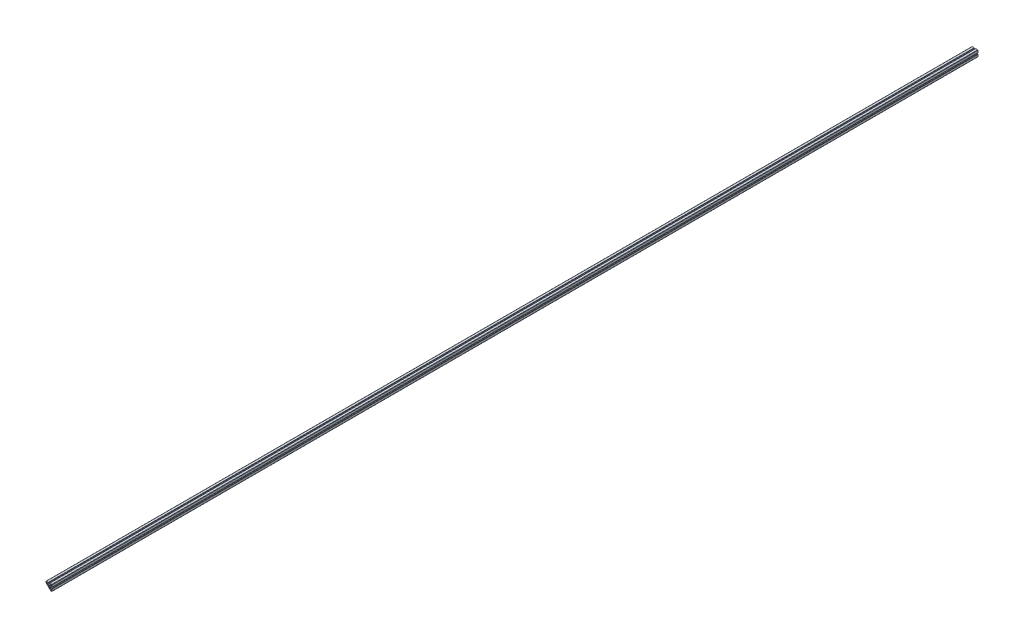
SolidWorks part; units mm, degrees
ref_plane "Front Plane" through (0, 0, 0) normal (0, 0, 1) x (1, 0, 0)
ref_plane "Top Plane" through (0, 0, 0) normal (0, 1, 0) x (1, 0, 0)
ref_plane "Right Plane" through (0, 0, 0) normal (1, 0, 0) x (0, 0, -1)
sketch "Sketch1" plane through (0, 0, 0) normal (0, 0, 1) x (1, 0, 0)
  line L0 (0, 0) -> (20, 20) construction
  line L1 (0, 0) -> (0, 20) construction
  line L2 (0, -20) -> (0, 20) construction
  line L3 (20, 0) -> (-20, 0) construction
  line L4 (4.05, 20) -> (-4.05, 20) construction
  line L5 (-20, 20) -> (-4.05, 20) construction
  line L6 (0, 0) -> (-20, 20) construction
  line L7 (5.4787, 7.6) -> (-5.4787, 7.6) construction
  line L8 (5.4787, 7.6) -> (11.2, 13.3213) construction
  line L9 (11.2, 13.3213) -> (11.2, 18.5) construction
  line L10 (11.2, 18.5) -> (7.05, 18.5) construction
  line L11 (7.05, 18.5) -> (7.05, 17.5) construction
  line L12 (4.05, 20) -> (4.05, 17.5) construction
  line L13 (4.05, 17.5) -> (7.05, 17.5) construction
  line L14 (-5.4787, 7.6) -> (-11.2, 13.3213) construction
  line L15 (-11.2, 13.3213) -> (-11.2, 18.5) construction
  line L16 (-11.2, 18.5) -> (-7.05, 18.5) construction
  line L17 (-7.05, 18.5) -> (-7.05, 17.5) construction
  line L18 (-4.05, 17.5) -> (-7.05, 17.5) construction
  line L19 (-4.05, 20) -> (-4.05, 17.5) construction
  line L21 (-20, 20) -> (-20, 10.5787) construction
  line L22 (-20, 10.5787) -> (-4.7107, -4.7107) construction
  line L23 (0, 0) -> (-4.7107, -4.7107) construction
  line L24 (-7.6, 5.4787) -> (-13.3213, 11.2) construction
  line L25 (-13.3213, 11.2) -> (-18.5, 11.2) construction
  line L26 (-18.5, 11.2) -> (-7.6, 0.3) construction
  line L27 (-7.6, 0.3) -> (-7.6, 5.4787) construction
  line L28 (-13.05, 5.75) -> (-14.1107, 4.6893) construction
  line L29 (11.2, 20) -> (11.2, 18.5) construction
  line L30 (4.05, 20) -> (20, 20) construction
  line L31 (-18.5, 18.5) -> (-14.5, 18.5) construction
  line L32 (-18.5, 18.5) -> (-18.5, 14.5) construction
  line L33 (-18.5, 14.5) -> (-14.5, 14.5) construction
  line L34 (-14.5, 18.5) -> (-14.5, 14.5) construction
  line L35 (-18.5, 18.5) -> (-14.5, 14.5) construction
  line L36 (-18.5, 14.5) -> (-14.5, 18.5) construction
  line L37 (18.5, 14.5) -> (14.5, 14.5) construction
  line L38 (18.5, 18.5) -> (18.5, 14.5) construction
  line L39 (18.5, 18.5) -> (14.5, 18.5) construction
  line L40 (14.5, 18.5) -> (14.5, 14.5) construction
  circle A0 centre (0, 0) radius 4.45 construction
  point P4 (0, 0)
  point P7 (0, 0)
  point P10 (0, 0)
  point P13 (0, 0)
  point P18 (0, 20)
  point P22 (0, 20)
  point P25 (0, 7.6)
  point P49 (-16.5, 16.5)
  dimension "D2" = 8.9
  dimension "D3" = 45
  dimension "D4" = 8.1
  dimension "D8" = 3
  dimension "D9" = 1
  dimension "D11" = 1.5
  dimension "D12" = 1.5
  dimension "D13" = 4
  dimension "D5" = 22.4
  dimension "D7" = 1.5
  dimension "D10" = 40
  dimension "D14" = 12.4
  dimension "D6" = 40
sketch "Sketch2" plane through (0, 0, 0) normal (1, 0, 0) x (0, 0, -1)
  line L0 (3048, 0) -> (-3048, 0) construction
  line L1 (-3008, -20) -> (-3008, 20) construction
  line L2 (3008, -20) -> (3008, 20) construction
  point P3 (0, 0)
  point P7 (-3008, 0)
  point P10 (3008, 0)
  dimension "Length" = 6096
  dimension "D1" = 40
  dimension "D2" = 40
  dimension "D3" = 40
sketch "Sketch3" plane through (0, 0, 0) normal (0, 0, 1) x (1, 0, 0)
  line L0 (18.5, 18.5) -> (14.5, 18.5) construction
  line L1 (14.5, 18.5) -> (14.5, 14.5) construction
  line L4 (4.05, 20) -> (20, 20) construction
  line L5 (0, 0) -> (20, 20) construction
  line L6 (11.2, 18.5) -> (7.05, 18.5) construction
  line L7 (7.05, 18.5) -> (7.05, 17.5) construction
  line L8 (4.05, 17.5) -> (7.05, 17.5) construction
  line L9 (4.05, 20) -> (4.05, 17.5) construction
  line L10 (-13.3213, 11.2) -> (-18.5, 11.2) construction
  line L11 (-18.5, 11.2) -> (-7.6, 0.3) construction
  line L12 (-7.6, 0.3) -> (-7.6, 5.4787) construction
  line L13 (-7.6, 5.4787) -> (-13.3213, 11.2) construction
  line L14 (-18.5, 18.5) -> (-14.5, 18.5) construction
  line L15 (-18.5, 18.5) -> (-18.5, 14.5) construction
  line L16 (-18.5, 14.5) -> (-14.5, 14.5) construction
  line L17 (-14.5, 18.5) -> (-14.5, 14.5) construction
  line L18 (-4.05, 20) -> (-4.05, 17.5) construction
  line L19 (-4.05, 17.5) -> (-7.05, 17.5) construction
  line L20 (-7.05, 18.5) -> (-7.05, 17.5) construction
  line L21 (-11.2, 18.5) -> (-7.05, 18.5) construction
  line L22 (-11.2, 13.3213) -> (-11.2, 18.5) construction
  line L23 (-5.4787, 7.6) -> (-11.2, 13.3213) construction
  line L24 (5.4787, 7.6) -> (-5.4787, 7.6) construction
  line L25 (5.4787, 7.6) -> (11.2, 13.3213) construction
  line L26 (11.2, 13.3213) -> (11.2, 18.5) construction
  line L27 (-20, 20) -> (-4.05, 20) construction
  line L28 (-20, 20) -> (-20, 10.5787) construction
  line L29 (-20, 10.5787) -> (-4.7107, -4.7107) construction
  line L30 (0, 0) -> (-4.7107, -4.7107) construction
  line L31 (18.5, 18.5) -> (14.5, 18.5)
  line L32 (14.5, 18.5) -> (14.5, 14.5)
  line L35 (4.05, 20) -> (20, 20)
  line L36 (3.1466, 3.1466) -> (14.5, 14.5)
  line L37 (11.2, 18.5) -> (7.05, 18.5)
  line L38 (7.05, 18.5) -> (7.05, 17.5)
  line L39 (4.05, 17.5) -> (7.05, 17.5)
  line L40 (4.05, 20) -> (4.05, 17.5)
  line L41 (-13.3213, 11.2) -> (-18.5, 11.2)
  line L42 (-18.5, 11.2) -> (-7.6, 0.3)
  line L43 (-7.6, 0.3) -> (-7.6, 5.4787)
  line L44 (-7.6, 5.4787) -> (-13.3213, 11.2)
  line L45 (-18.5, 18.5) -> (-14.5, 18.5)
  line L46 (-18.5, 18.5) -> (-18.5, 14.5)
  line L47 (-18.5, 14.5) -> (-14.5, 14.5)
  line L48 (-14.5, 18.5) -> (-14.5, 14.5)
  line L49 (-4.05, 20) -> (-4.05, 17.5)
  line L50 (-4.05, 17.5) -> (-7.05, 17.5)
  line L51 (-7.05, 18.5) -> (-7.05, 17.5)
  line L52 (-11.2, 18.5) -> (-7.05, 18.5)
  line L53 (-11.2, 13.3213) -> (-11.2, 18.5)
  line L54 (-5.4787, 7.6) -> (-11.2, 13.3213)
  line L55 (5.4787, 7.6) -> (-5.4787, 7.6)
  line L56 (5.4787, 7.6) -> (11.2, 13.3213)
  line L57 (11.2, 13.3213) -> (11.2, 18.5)
  line L58 (-20, 20) -> (-4.05, 20)
  line L59 (-20, 20) -> (-20, 10.5787)
  line L60 (-20, 10.5787) -> (-4.7107, -4.7107)
  line L61 (-3.1466, -3.1466) -> (-4.7107, -4.7107)
  line L62 (18.5, 18.5) -> (20, 20)
  circle A0 centre (0, 0) radius 4.45 construction
  arc A1 (3.1466, 3.1466) -> (-3.1466, -3.1466) centre (0, 0) ccw
extrude "Boss-Extrude1" add sketch "Sketch3" along normal mid plane 6096
fillet "Fillet1" radius 2 6 edges at (-18.5, 18.5, 0) (-5.4787, 7.6, 0) (-20, 20, 0) (-11.2, 18.5, 0) (11.2, 18.5, 0) (5.4787, 7.6, 0)
fillet "Fillet3" radius 0.5 7 edges at (-7.6, 5.4787, 0) (-7.6, 0.3, 0) (-18.5, 11.2, 0) (4.05, 20, 0) (4.05, 17.5, 0) (-4.05, 17.5, 0) (-4.05, 20, 0)
mirror "Mirror1" about plane through (3.1466, 3.1466, 3048) normal (-0.7071, 0.7071, 0) of bodies 104
fillet "Fillet2" radius 2 2 edges at (18.5, 18.5, 0) (20, 20, 0)
equation "\"D12@Sketch1\"=\"D11@Sketch1\""
equation "\"D1@Boss-Extrude1\"=\"Length@Sketch2\""
equation "\"D3@Sketch2\"=\"D2@Sketch2\""
